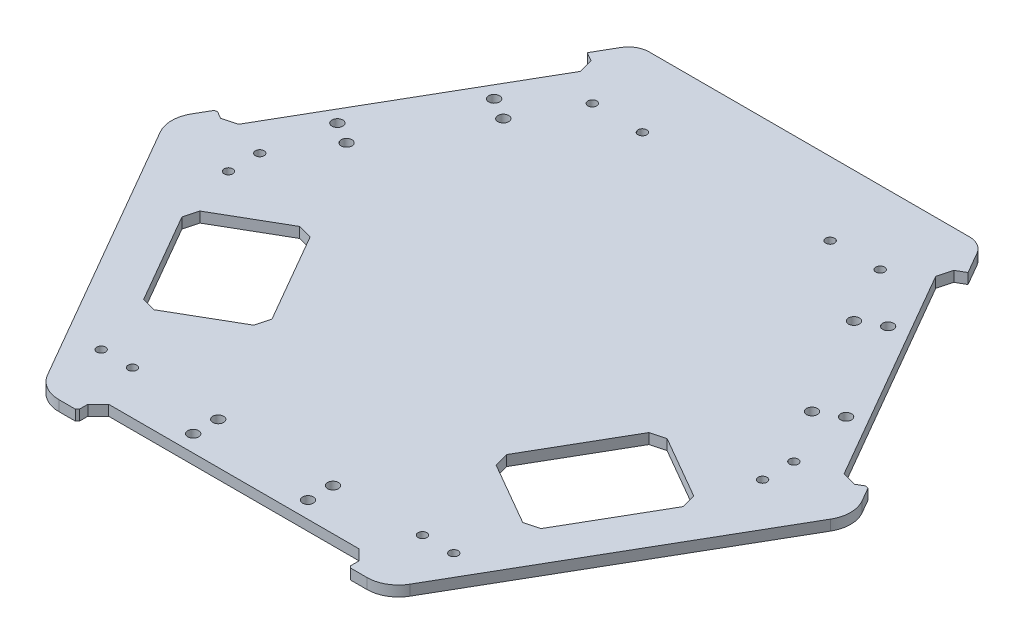
SolidWorks part; units mm, degrees
material "5052-H32"
ref_plane "前基準面" through (0, 0, 0) normal (0, 0, 1) x (1, 0, 0)
ref_plane "上基準面" through (0, 0, 0) normal (0, 1, 0) x (1, 0, 0)
ref_plane "右基準面" through (0, 0, 0) normal (1, 0, 0) x (0, 0, -1)
sketch "草圖1" plane through (0, 0, 0) normal (0, 1, 0) x (1, 0, 0)
  line L1 (82.5, 142.8942) -> (-82.5, 142.8942)
  line L2 (-82.5, 142.8942) -> (-165, 0)
  line L3 (-165, 0) -> (-82.5, -142.8942)
  line L4 (-82.5, -142.8942) -> (82.5, -142.8942)
  line L5 (82.5, -142.8942) -> (165, 0)
  line L6 (165, 0) -> (82.5, 142.8942)
  circle A0 centre (0, 0) radius 142.8942 construction
  dimension "D1" = 165
extrude "填料-伸長1" add sketch "草圖1" along normal blind 5
sketch "草圖2" plane through (0, 5, 0) normal (0, 1, 0) x (1, 0, 0)
  line L1 (-65, -132.8942) -> (65, -132.8942)
  line L2 (-65, -132.8942) -> (-65, -142.8942)
  line L3 (-65, -142.8942) -> (65, -142.8942)
  line L4 (65, -132.8942) -> (65, -142.8942)
  line L5 (-82.5, -142.8942) -> (82.5, -142.8942) construction
  point P6 (0, -142.8942)
  dimension "D1" = 130
  dimension "D2" = 10
extrude "除料-伸長1" cut sketch "草圖2" against normal blind 5
ref_axis "基準軸1" through (0, 142.8942, 0) along (0, -1, 0)
sketch "草圖9" plane through (0, 5, 0) normal (0, 1, 0) x (1, 0, 0)
  line L0 (-27.5, -112.8942) -> (27.5, -112.8942) construction
  line L1 (27.5, -112.8942) -> (27.5, -124.8942) construction
  line L2 (-27.5, -112.8942) -> (-27.5, -124.8942) construction
  line L3 (-27.5, -124.8942) -> (27.5, -124.8942) construction
  line L4 (0, -124.8942) -> (0, -132.8942) construction
  line L5 (65, -132.8942) -> (-65, -132.8942) construction
  circle A0 centre (-27.5, -124.8942) radius 2.6
  circle A1 centre (-27.5, -112.8942) radius 2.6
  circle A2 centre (27.5, -112.8942) radius 2.6
  circle A3 centre (27.5, -124.8942) radius 2.6
  dimension "D1" = 5.2
  dimension "D2" = 8
  dimension "D3" = 12
  dimension "D4" = 55
extrude "除料-伸長8" cut sketch "草圖9" against normal through all and the other way through all
pattern_circular "環狀複製排列1" count 3 over 360 about axis through (0, 142.8942, 0) along (0, -1, 0) of "除料-伸長1", "除料-伸長8"
sketch "草圖4" plane through (0, 5, 0) normal (0, 1, 0) x (1, 0, 0)
  line L0 (-128, -7.5) -> (-128, 7.5) construction
  circle A0 centre (-128, 7.5) radius 2.1
  circle A1 centre (-128, -7.5) radius 2.1
  point P5 (-128, 0)
  dimension "D2" = 4.2
  dimension "D1" = 15
  dimension "D3" = 128
  dimension "D4" = 0
extrude "除料-伸長4" cut sketch "草圖4" against normal through all
sketch "草圖5" plane through (0, 5, 0) normal (0, 1, 0) x (1, 0, 0)
  line L0 (0, 0) -> (0, -112) construction
  line L1 (0, -112) -> (-77, -112) construction
  line L2 (-84.5, -112) -> (-69.5, -112) construction
  circle A0 centre (-84.5, -112) radius 2.1
  circle A1 centre (-69.5, -112) radius 2.1
  circle A2 centre (84.5, -112) radius 2.1
  circle A3 centre (69.5, -112) radius 2.1
  point P8 (-77, -112)
  dimension "D1" = 4.2
  dimension "D2" = 15
  dimension "D3" = 112
  dimension "D4" = 77
extrude "除料-伸長5" cut sketch "草圖5" against normal through all
sketch "草圖8" plane through (0, 5, 0) normal (0, 1, 0) x (1, 0, 0)
  line L0 (-122.6795, -33.3013) -> (-92.6795, -85.2628)
  line L1 (-122.6795, -33.3013) -> (-83.7083, -10.8013)
  line L2 (-92.6795, -85.2628) -> (-53.7083, -62.7628)
  line L3 (-83.7083, -10.8013) -> (-53.7083, -62.7628)
  line L5 (-165, 0) -> (-82.5, -142.8942) construction
  line L6 (-165, 0) -> (-140, -43.3013) construction
  line L7 (-140, -43.3013) -> (-122.6795, -33.3013) construction
  dimension "D1" = 45
  dimension "D2" = 60
  dimension "D3" = 20
  dimension "D4" = 50
extrude "除料-伸長7" cut sketch "草圖8" against normal through all
chamfer "導角2" distance 5 angle 45 4 edges at (-53.7083, 2.5, 62.7628) (-92.6795, 2.5, 85.2628) (-122.6795, 2.5, 33.3013) (-83.7083, 2.5, 10.8013)
mirror "鏡射1" about plane through (0, 0, 0) normal (1, 0, 0) of "除料-伸長7", "除料-伸長4", "導角2"
chamfer "導角1" distance 5 angle 45 6 edges at (147.5897, 2.5, -10.1554) (65, 2.5, 132.8942) (-65, 2.5, 132.8942) (-147.5897, 2.5, -10.1554) (82.5897, 2.5, -122.7387) (-82.5897, 2.5, -122.7387)
fillet "圓角2" radius 15 4 edges at (-165, 2.5, 0) (-82.5, 2.5, 142.8942) (82.5, 2.5, 142.8942) (165, 2.5, 0)
chamfer "導角3" distance 1 angle 45 4 edges at (65, 2.5, 142.8942) (-65, 2.5, 142.8942) (156.25, 2.5, -15.1554) (-156.25, 2.5, -15.1554)
sketch "草圖15" plane through (0, 5, 0) normal (0, 1, 0) x (1, 0, 0)
  line L2 (82.5, 142.8942) -> (-82.5, 142.8942) construction
  circle A0 centre (-69, 107.8942) radius 2.1
  circle A1 centre (-45, 107.8942) radius 2.1
  point P6 (0, 142.8942)
  dimension "D1" = 4.2
  dimension "D2" = 35
  dimension "D3" = 69
  dimension "D4" = 24
extrude "除料-伸長15" cut sketch "草圖15" against normal through all
mirror "鏡射2" about plane through (0, 0, 0) normal (1, 0, 0) of "除料-伸長15"
fillet "圓角3" radius 10 2 edges at (82.5, 2.5, -142.8942) (-82.5, 2.5, -142.8942)
